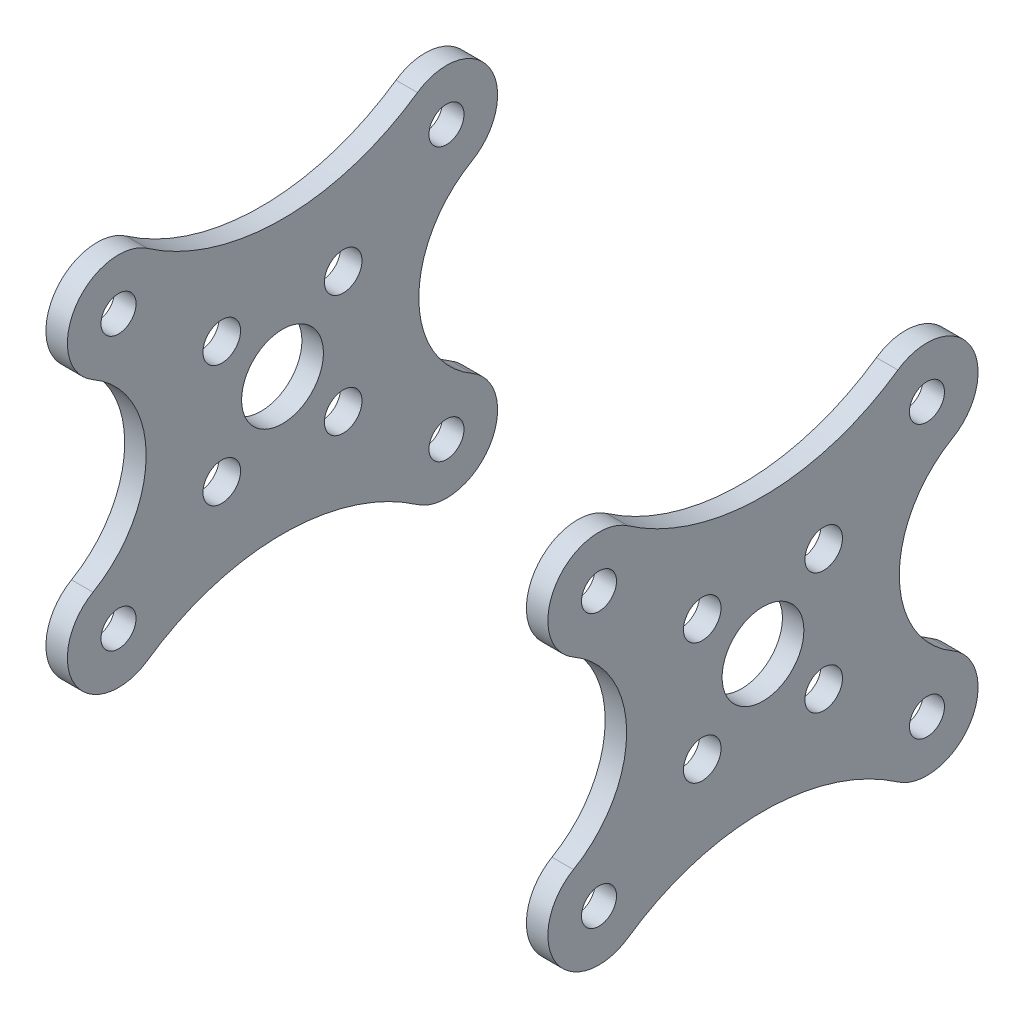
SolidWorks part; units mm, degrees
material "TPU"
ref_plane "Front Plane" through (0, 0, 0) normal (0, 0, 1) x (1, 0, 0)
ref_plane "Top Plane" through (0, 0, 0) normal (0, 1, 0) x (1, 0, 0)
ref_plane "Right Plane" through (0, 0, 0) normal (1, 0, 0) x (0, 0, -1)
ref_plane "Plane2" through (23.38, 0, 0) normal (1, 0, 0) x (0, 0, -1)
sketch "Sketch1" plane through (23.38, 0, 0) normal (1, 0, 0) x (0, 0, -1)
  line L0 (-18.2721, 15.875) -> (-97.3447, 15.875) construction
  circle A0 centre (-40.279, 12.7) radius 3.175 construction
  circle A1 centre (-9.7272, 12.7) radius 3.175 construction
  circle A2 centre (-9.7272, -12.7) radius 3.175 construction
  circle A3 centre (-40.279, -12.7) radius 3.175 construction
  circle A4 centre (-40.279, 12.7) radius 4.3656 construction
  circle A5 centre (-9.7272, 12.7) radius 4.3656 construction
  circle A6 centre (-9.7272, -12.7) radius 4.3656 construction
  circle A7 centre (-40.279, -12.7) radius 4.3656 construction
  circle A8 centre (-40.279, 12.7) radius 1.4224 construction
  circle A9 centre (-25.0031, 0) radius 12.7 construction
  arc A10 (-12.4337, 16.6187) -> (-7.3489, 8.5739) centre (-9.7272, 12.7) cw
  arc A11 (-7.3489, -8.5739) -> (-12.4337, -16.6187) centre (-9.7272, -12.7) cw
  arc A12 (-37.5725, -16.6187) -> (-42.6573, -8.5739) centre (-40.279, -12.7) cw
  arc A13 (-42.6573, 8.5739) -> (-37.5725, 16.6187) centre (-40.279, 12.7) cw
  circle A14 centre (-25.0031, 0) radius 15.5 construction
  arc A15 (-42.6573, 8.5739) -> (-42.6573, -8.5739) centre (-47.5993, 0) cw
  arc A16 (-7.3489, -8.5739) -> (-7.3489, 8.5739) centre (-2.407, 0) cw
  arc A17 (-37.5725, 16.6187) -> (-12.4337, 16.6187) centre (-25.0031, 34.8178) ccw
  arc A18 (-37.5725, -16.6187) -> (-12.4337, -16.6187) centre (-25.0031, -34.8178) cw
  circle A21 centre (-25.0031, 0) radius 15.5 construction
  dimension "D1" = 6.35
  dimension "D2" = 1.1906
  dimension "D3" = 2.8448
  dimension "D4" = 1.5875
  dimension "D5" = 25.4
extrude "Boss-Extrude1" add sketch "Sketch1" against normal blind 2
sketch "Sketch2" plane through (21.38, 0, 0) normal (-1, 0, 0) x (0, 0, 1)
  line L0 (47.5993, 0) -> (2.407, 0) construction
  line L3 (25.0031, 12.7) -> (25.0031, -12.7) construction
  line L7 (19.3463, -5.6569) -> (30.66, 5.6569) construction
  line L8 (19.3463, 5.6569) -> (30.66, -5.6569) construction
  circle A1 centre (19.3463, 5.6569) radius 1.75
  circle A2 centre (19.3463, -5.6569) radius 1.75
  circle A3 centre (30.66, -5.6569) radius 1.75
  circle A4 centre (30.66, 5.6569) radius 1.75
  arc A5 (42.6573, 8.5739) -> (42.6573, -8.5739) centre (47.5993, 0) ccw construction
  arc A6 (7.3489, -8.5739) -> (7.3489, 8.5739) centre (2.407, 0) ccw construction
  arc A7 (12.4337, 16.6187) -> (37.5725, 16.6187) centre (25.0031, 34.8178) ccw construction
  circle A8 centre (25.0031, 0) radius 3.81
  point P16 (25.0031, 0)
  dimension "D4" = 3.5
  dimension "D5" = 7.62
  dimension "D1" = 16
  dimension "D2" = 16
  dimension "D3" = 45
extrude "Cut-Extrude1" cut sketch "Sketch2" against normal up to surface (2 mm away)
sketch "Sketch4" [suppressed] plane through (25.92, 0, 0) normal (1, 0, 0) x (0, 0, -1)
  circle A0 centre (-14.4897, 12.7) radius 4.7625
  circle A1 centre (-45.0415, 12.7) radius 4.7625
  circle A2 centre (-45.0415, -12.7) radius 4.7625
  circle A3 centre (-14.4897, -12.7) radius 4.7625
  arc A4 (-15.6935, -17.3078) -> (-10.8058, -9.6817) centre (-14.4897, -12.7) ccw construction
  arc A5 (-10.8058, 9.6817) -> (-15.6935, 17.3078) centre (-14.4897, 12.7) ccw construction
  arc A6 (-43.8377, 17.3078) -> (-48.7254, 9.6817) centre (-45.0415, 12.7) ccw construction
  arc A7 (-48.7254, -9.6817) -> (-43.8377, -17.3078) centre (-45.0415, -12.7) ccw construction
extrude "Boss-Extrude2" [suppressed] add sketch "Sketch4" against normal up to surface (11.43 mm away)
fillet "Fillet1" [suppressed] radius 2.54
hole_wizard "#4 Clearance Hole1" positions "Sketch6" profile "Sketch8" hole size "#4" standard "ANSI Inch" end condition up to next
sketch "Sketch6" plane through (21.38, 0, 0) normal (1, 0, 0) x (0, 0, -1)
  arc A0 (-37.5725, 16.6187) -> (-42.6573, 8.5739) centre (-40.279, 12.7) ccw construction
  arc A1 (-7.3489, 8.5739) -> (-12.4337, 16.6187) centre (-9.7272, 12.7) ccw construction
  arc A2 (-12.4337, -16.6187) -> (-7.3489, -8.5739) centre (-9.7272, -12.7) ccw construction
  arc A3 (-42.6573, -8.5739) -> (-37.5725, -16.6187) centre (-40.279, -12.7) ccw construction
  point P0 (-40.279, 12.7)
  point P3 (-9.7272, 12.7)
  point P6 (-9.7272, -12.7)
  point P9 (-40.279, -12.7)
sketch "Sketch8" plane through (21.38, 12.7, 40.279) normal (0, 1, 0) x (0, 0, 1)
  line L0 (0, 0) -> (0, 2)
  line L1 (0, 2) -> (1.6319, 2)
  line L2 (1.6319, 2) -> (1.6319, 0)
  line L5 (1.6319, 0) -> (0, 0)
  line L11 (0, -6.35) -> (0, 107.95) construction
  dimension "Thru Hole Dia." = 3.2639
  dimension "Thru Hole Depth" = 2
chamfer "Chamfer1" [suppressed] distance 2.032 angle 45
mirror "Mirror1" about plane through (0, 0, 0) normal (1, 0, 0) of bodies 106 104
equation "\"D1@Sketch2\"=16mm"
equation "\"D2@Sketch2\"=16mm"
equation "\"D1@Boss-Extrude1\"=2mm"
